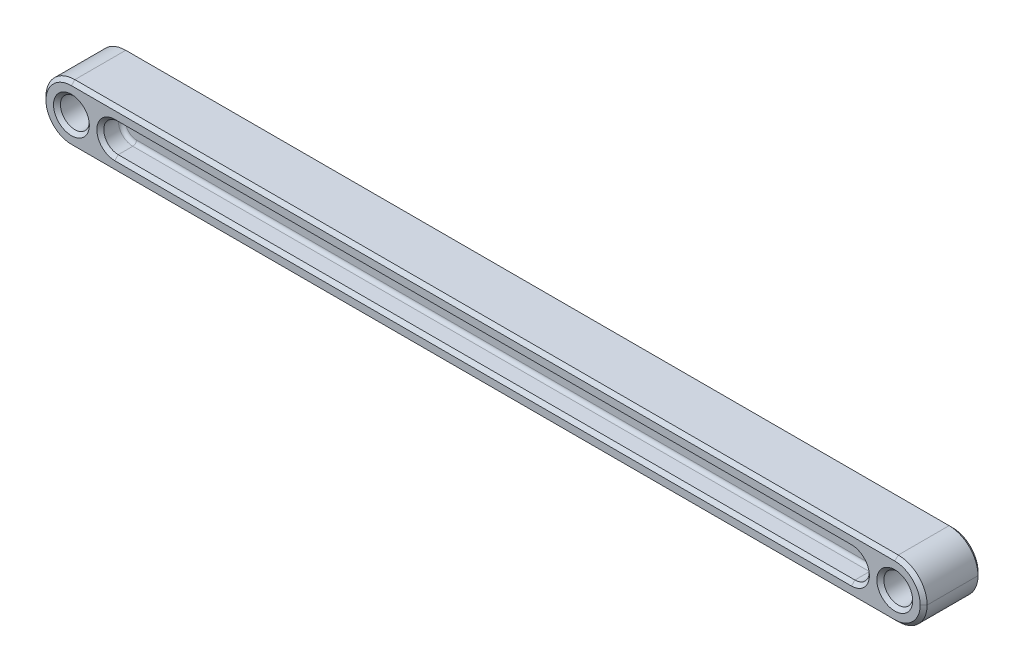
SolidWorks part; units mm, degrees
ref_plane "Front Plane" through (0, 0, 0) normal (0, 0, 1) x (1, 0, 0)
ref_plane "Top Plane" through (0, 0, 0) normal (0, 1, 0) x (1, 0, 0)
ref_plane "Right Plane" through (0, 0, 0) normal (1, 0, 0) x (0, 0, -1)
sketch "Sketch1" plane through (0, 0, 0) normal (1, 0, 0) x (0, 0, -1)
  line L1 (-6.35, -6.35) -> (6.35, -6.35)
  line L2 (-6.35, -6.35) -> (-6.35, 6.35)
  line L3 (-6.35, 6.35) -> (6.35, 6.35)
  line L4 (6.35, -6.35) -> (6.35, 6.35)
  line L5 (-6.35, -6.35) -> (6.35, 6.35) construction
  line L6 (-6.35, 6.35) -> (6.35, -6.35) construction
  point P0 (0, 0)
  dimension "D1" = 12.7
extrude "Boss-Extrude1" add sketch "Sketch1" along normal mid plane 193.675 contours L3 L4 L1 L2
hole_wizard "1/4 (0.25) Diameter Hole1" positions "Sketch2" profile "Sketch3" hole size "1/4" standard "ANSI Inch" end condition through all
sketch "Sketch2" plane through (0, 0, 6.35) normal (0, 0, 1) x (1, 0, 0)
  line L0 (-90.4875, 0) -> (90.4875, 0) construction
  line L2 (-96.8375, -6.35) -> (-96.8375, 6.35) construction
  point P0 (-90.4875, 0)
  point P2 (90.4875, 0)
  dimension "D1" = 6.35
sketch "Sketch3" plane through (-90.4875, 0, 6.35) normal (1, 0, 0) x (0, -1, 0)
  line L0 (0, 0) -> (0, 12.7)
  line L1 (0, 12.7) -> (3.175, 12.7)
  line L2 (3.175, 12.7) -> (3.175, 0)
  line L5 (3.175, 0) -> (0, 0)
  line L11 (0, -6.35) -> (0, 107.95) construction
  dimension "Thru Hole Dia." = 6.35
  dimension "Thru Hole Depth" = 12.7
sketch "Sketch6" plane through (0, 0, 0) normal (0, 0, 1) x (1, 0, 0)
  line L0 (-80.9625, 0) -> (80.9625, 0) construction
  line L1 (-80.9625, 3.175) -> (80.9625, 3.175)
  line L2 (-80.9625, -3.175) -> (80.9625, -3.175)
  line L3 (96.8375, 6.35) -> (-96.8375, 6.35) construction
  arc A0 (-80.9625, 3.175) -> (-80.9625, -3.175) centre (-80.9625, 0) ccw
  arc A1 (80.9625, -3.175) -> (80.9625, 3.175) centre (80.9625, 0) ccw
  point P2 (0, 0)
  dimension "D1" = 161.925
  dimension "D2" = 3.175
extrude "Cut-Extrude1" cut sketch "Sketch6" against normal blind 4.7625 from surface contours L2 A1 L1 A0 starting at face at (-87.3125, 0, 6.35)
extrude "Cut-Extrude2" cut sketch "Sketch6<3>" along normal blind 4.7625 from surface starting at face at (-87.3125, 0, -6.35)
sketch "Sketch6<3>" plane through (0, 0, 0) normal (0, 0, 1) x (1, 0, 0) same geometry as "Sketch6"
fillet "Fillet1" radius 6.35 4 edges at (96.8375, -6.35, 0) (96.8375, 6.35, 0) (-96.8375, -6.35, 0) (-96.8375, 6.35, 0)
fillet "Fillet2" radius 0.7937 8 edges at (84.1375, 0, -1.5875) (0, -3.175, -1.5875) (-84.1375, 0, -1.5875) (84.1375, 0, 1.5875) (0, -3.175, 1.5875) (-84.1375, 0, 1.5875) (0, 3.175, -1.5875) (0, 3.175, 1.5875)
chamfer "Chamfer1" distance 0.762 angle 45 24 edges at (93.6625, 0, 6.35) (93.6625, 0, -6.35) (-87.3125, 0, 6.35) (-87.3125, 0, -6.35) (0, 3.175, 6.35) (84.1375, 0, 6.35) (-84.1375, 0, 6.35) (0, -3.175, 6.35) (0, 3.175, -6.35) (-84.1375, 0, -6.35) (84.1375, 0, -6.35) (0, -3.175, -6.35) (0, 6.35, 6.35) (94.9776, 4.4901, 6.35) (-94.9776, 4.4901, 6.35) (94.9776, -4.4901, 6.35) (-94.9776, -4.4901, 6.35) (0, -6.35, 6.35) (0, 6.35, -6.35) (94.9776, 4.4901, -6.35) (-94.9776, 4.4901, -6.35) (94.9776, -4.4901, -6.35) (-94.9776, -4.4901, -6.35) (0, -6.35, -6.35)
